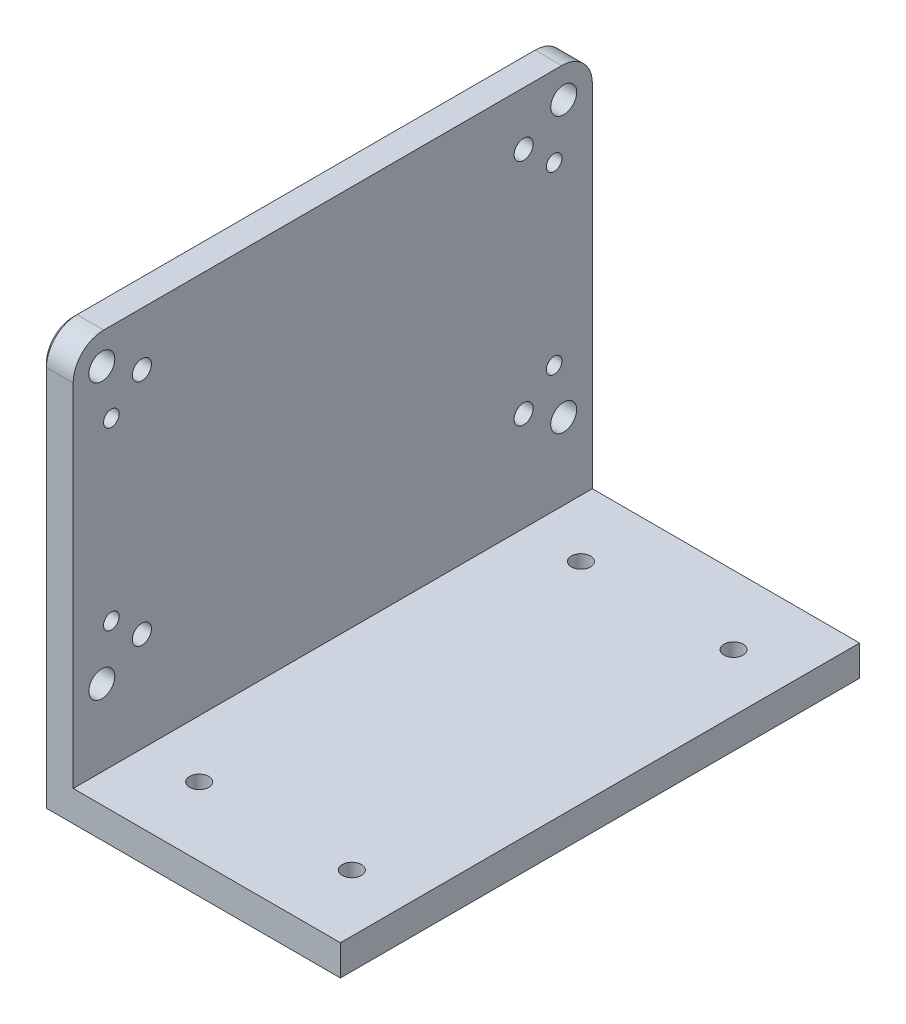
SolidWorks part; units mm, degrees
material "6061-T6 (SS)"
ref_plane "Front Plane" through (0, 0, 0) normal (0, 0, 1) x (1, 0, 0)
ref_plane "Top Plane" through (0, 0, 0) normal (0, 1, 0) x (1, 0, 0)
ref_plane "Right Plane" through (0, 0, 0) normal (1, 0, 0) x (0, 0, -1)
sketch "Sketch1" plane through (0, 0, 0) normal (0, 0, 1) x (1, 0, 0)
  line L0 (0, 0) -> (39, 0)
  line L1 (39, 0) -> (39, 4)
  line L2 (39, 4) -> (4, 4)
  line L3 (4, 4) -> (4, 54)
  line L4 (4, 54) -> (0, 54)
  line L5 (0, 54) -> (0, 0)
  dimension "D1" = 50
  dimension "D2" = 35
  dimension "D3" = 4
extrude "Boss-Extrude1" add sketch "Sketch1" along normal blind 68
sketch "Sketch2" plane through (4, 0, 0) normal (1, 0, 0) x (0, 0, -1)
  line L0 (-34, 32) -> (-34, 54) construction
  line L1 (-64.25, 50) -> (-3.75, 50) construction
  line L2 (-64.25, 50) -> (-64.25, 14) construction
  line L3 (-64.25, 14) -> (-3.75, 14) construction
  line L4 (-3.75, 50) -> (-3.75, 14) construction
  line L5 (-64.25, 50) -> (-3.75, 14) construction
  line L6 (-64.25, 14) -> (-3.75, 50) construction
  line L7 (-68, 54) -> (0, 54) construction
  point P0 (-34, 32)
  dimension "D1" = 60.5
  dimension "D2" = 36
  dimension "D3" = 4
hole_wizard "M3 Clearance Hole1" positions "Sketch4" profile "Sketch3" hole size "M3" standard "ANSI Metric"
sketch "Sketch4" plane through (4, 0, 0) normal (1, 0, 0) x (0, 0, -1)
  point P0 (-64.25, 50)
  point P3 (-3.75, 50)
  point P6 (-3.75, 14)
  point P9 (-64.25, 14)
sketch "Sketch3" plane through (4, 50, 64.25) normal (0, 1, 0) x (0, 0, -1)
  line L0 (0, 0) -> (0, 6.0215)
  line L1 (0, 6.0215) -> (1.7, 5)
  line L2 (1.7, 5) -> (1.7, 0)
  line L5 (1.7, 0) -> (0, 0)
  line L10 (0, 6.0215) -> (-1.7, 5) construction
  line L11 (0, -6.35) -> (0, 107.95) construction
  dimension "Hole Dia." = 3.4
  dimension "Hole Depth" = 5
  dimension "Drill Angle" = 118
sketch "Sketch5" plane through (0, 4, 0) normal (0, 1, 0) x (1, 0, 0)
  line L0 (21.5, 0) -> (21.5, -68) construction
  line L1 (39, 0) -> (4, 0) construction
  line L2 (39, -68) -> (4, -68) construction
  line L3 (4, -34) -> (39, -34) construction
  line L4 (4, -68) -> (4, 0) construction
  line L5 (39, -68) -> (39, 0) construction
  line L7 (11.5, -59) -> (31.5, -59) construction
  line L8 (11.5, -59) -> (11.5, -9) construction
  line L9 (11.5, -9) -> (31.5, -9) construction
  line L10 (31.5, -59) -> (31.5, -9) construction
  line L11 (11.5, -59) -> (31.5, -9) construction
  line L12 (11.5, -9) -> (31.5, -59) construction
  point P12 (21.5, -34)
  dimension "D1" = 20
  dimension "D2" = 50
hole_wizard "M3x0.5 Tapped Hole1" positions "Sketch7" profile "Sketch6" tap size "M3x0.5" standard "ANSI Metric"
sketch "Sketch7" plane through (0, 4, 0) normal (0, 1, 0) x (1, 0, 0)
  point P0 (31.5, -59)
  point P3 (11.5, -59)
  point P6 (11.5, -9)
  point P9 (31.5, -9)
sketch "Sketch6" plane through (31.5, 4, 59) normal (1, 0, 0) x (0, 0, 1)
  line L0 (0, 0) -> (0, 8.7511)
  line L1 (0, 8.7511) -> (1.25, 8)
  line L2 (1.25, 8) -> (1.25, 0)
  line L5 (1.25, 0) -> (0, 0)
  line L10 (0, 8.7511) -> (-1.25, 8) construction
  line L11 (0, -6.35) -> (0, 107.95) construction
  dimension "Tap Drill Dia." = 2.5
  dimension "Tap Drill Depth" = 8
  dimension "Drill Angle" = 118
fillet "Fillet1" radius 4 2 edges at (2, 54, 68) (2, 54, 0)
chamfer "Chamfer1" distance 0.5 angle 45 5 edges at (0, 25, 68) (0, 52.8284, 66.8284) (0, 54, 34) (0, 52.8284, 1.1716) (0, 25, 0)
sketch "Sketch8" plane through (0, 0, 0) normal (-1, 0, 0) x (0, 0, 1)
  line L0 (34, 0) -> (34, 32) construction
  line L1 (5, 20.5) -> (63, 20.5)
  line L2 (5, 20.5) -> (5, 43.5)
  line L3 (5, 43.5) -> (63, 43.5)
  line L4 (63, 20.5) -> (63, 43.5)
  line L5 (5, 20.5) -> (63, 43.5) construction
  line L6 (5, 43.5) -> (63, 20.5) construction
  line L7 (67.5, 0) -> (0.5, 0) construction
  line L8 (3.75, 50) -> (64.25, 14) construction
  point P0 (34, 32)
  point P13 (34, 32)
  dimension "D1" = 58
  dimension "D2" = 23
hole_wizard "M2.5x0.45 Tapped Hole1" positions "Sketch10" profile "Sketch9" tap size "M2.5x0.45" standard "ANSI Metric"
sketch "Sketch10" plane through (0, 0, 0) normal (-1, 0, 0) x (0, 0, 1)
  point P0 (5, 43.5)
  point P3 (63, 43.5)
  point P6 (63, 20.5)
  point P9 (5, 20.5)
sketch "Sketch9" plane through (0, 43.5, 5) normal (0, 1, 0) x (0, 0, 1)
  line L0 (0, 0) -> (0, 7.8659)
  line L1 (0, 7.8659) -> (1.025, 7.25)
  line L2 (1.025, 7.25) -> (1.025, 0)
  line L5 (1.025, 0) -> (0, 0)
  line L10 (0, 7.8659) -> (-1.025, 7.25) construction
  line L11 (0, -6.35) -> (0, 107.95) construction
  dimension "Tap Drill Dia." = 2.05
  dimension "Tap Drill Depth" = 7.25
  dimension "Drill Angle" = 118
sketch "Sketch11" plane through (0, 0, 0) normal (-1, 0, 0) x (0, 0, 1)
  line L1 (59, 17) -> (9, 17)
  line L2 (59, 17) -> (59, 47)
  line L3 (59, 47) -> (9, 47)
  line L4 (9, 17) -> (9, 47)
  line L5 (59, 17) -> (9, 47) construction
  line L6 (59, 47) -> (9, 17) construction
  point P0 (34, 32)
  dimension "D1" = 50
  dimension "D2" = 30
hole_wizard "M3x0.5 Tapped Hole3" positions "Sketch13" profile "Sketch12" tap size "M3x0.5" standard "ANSI Metric"
sketch "Sketch13" plane through (0, 0, 0) normal (-1, 0, 0) x (0, 0, 1)
  point P0 (9, 17)
  point P3 (9, 47)
  point P6 (59, 47)
  point P9 (59, 17)
sketch "Sketch12" plane through (0, 17, 9) normal (0, 1, 0) x (0, 0, 1)
  line L0 (0, 0) -> (0, 9.2511)
  line L1 (0, 9.2511) -> (1.25, 8.5)
  line L2 (1.25, 8.5) -> (1.25, 0)
  line L5 (1.25, 0) -> (0, 0)
  line L10 (0, 9.2511) -> (-1.25, 8.5) construction
  line L11 (0, -6.35) -> (0, 107.95) construction
  dimension "Tap Drill Dia." = 2.5
  dimension "Tap Drill Depth" = 8.5
  dimension "Drill Angle" = 118
